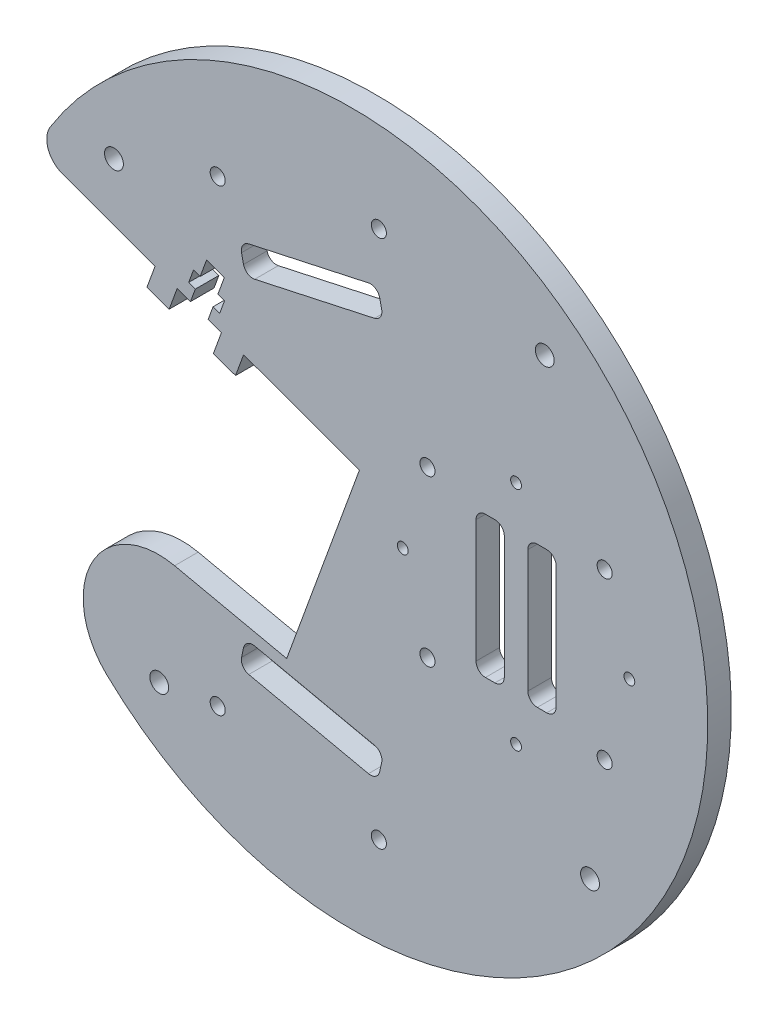
SolidWorks part; units mm, degrees
ref_plane "Plan de face" through (0, 0, 0) normal (0, 0, 1) x (1, 0, 0)
ref_plane "Plan de dessus" through (0, 0, 0) normal (0, 1, 0) x (1, 0, 0)
ref_plane "Plan de droite" through (0, 0, 0) normal (1, 0, 0) x (0, 0, -1)
sketch "Esquisse1" plane through (0, 0, 0) normal (0, 0, 1) x (1, 0, 0)
  line L0 (-41.7896, 25.5149) -> (-67.0437, 34.7187)
  line L3 (-22.9986, 18.6666) -> (1.5696, 9.7128)
  line L4 (1.5696, 9.7128) -> (-13.858, -32.6189)
  line L5 (-13.858, -32.6189) -> (-72.862, -19.7834)
  line L6 (-40.9058, -50.5145) -> (40.9058, 50.5145) construction
  line L7 (0, 0) -> (50.5145, -40.9058) construction
  line L8 (0, 0) -> (-50.5145, 40.9058) construction
  circle A0 centre (0, 0) radius 75.5 construction
  arc A1 (-67.0437, 34.7187) -> (-72.862, -19.7834) centre (0, 0) cw
  circle A2 centre (0, 0) radius 65 construction
  circle A3 centre (40.9058, 50.5145) radius 2
  circle A4 centre (-50.5145, 40.9058) radius 2
  circle A5 centre (50.5145, -40.9058) radius 2
  circle A6 centre (-40.9058, -50.5145) radius 2
  point P4 (-36.0291, 0)
  point P13 (-11.3975, 52.3938)
  point P22 (34.8192, 0)
  line B0 (-28.4976, 48.6739) -> (5.7025, 56.1137) construction
  line B1 (-14.416, 66.2693) -> (-7.4013, 34.0235) construction
  line B2 (-45.6847, 59.4672) -> (16.8527, 73.0714) construction
  line B3 (-49.5076, 53.5187) -> (-43.5558, 26.1586) construction
  line B4 (-43.5558, 26.1586) -> (28.7531, 41.8884) construction
  line B5 (22.8013, 69.2485) -> (28.7531, 41.8884) construction
  circle B6 centre (-28.4976, 48.6739) radius 1.6
  circle B7 centre (5.7025, 56.1137) radius 1.6
  circle B8 centre (5.7025, 56.1137) radius 16.6 construction
  circle B9 centre (-28.4976, 48.6739) radius 16.6 construction
  arc B10 (-45.6847, 59.4672) -> (-49.5076, 53.5187) centre (-44.6218, 54.5815) ccw construction
  arc B11 (16.8527, 73.0714) -> (22.8013, 69.2485) centre (17.9156, 68.1856) cw construction
  line B12 (-23.0151, 35.2322) -> (-23.4402, 37.1864)
  line B13 (-20.6357, 33.703) -> (4.7702, 39.2297)
  line B14 (6.2993, 41.6091) -> (5.8742, 43.5634)
  line B15 (-21.911, 39.5659) -> (3.4948, 45.0926)
  line B16 (-23.2276, 36.2093) -> (6.0868, 42.5862) construction
  arc B17 (3.4948, 45.0926) -> (5.8742, 43.5634) centre (3.9199, 43.1383) cw
  arc B18 (4.7702, 39.2297) -> (6.2993, 41.6091) centre (4.345, 41.184) ccw
  arc B19 (-20.6357, 33.703) -> (-23.0151, 35.2322) centre (-21.0608, 35.6573) cw
  arc B20 (-23.4402, 37.1864) -> (-21.911, 39.5659) centre (-21.4859, 37.6116) cw
  line B21 (5.7025, -56.1137) -> (-28.4976, -48.6739) construction
  line B22 (-14.416, -66.2693) -> (-7.4013, -34.0235) construction
  line B23 (16.8527, -73.0714) -> (-45.6847, -59.4672) construction
  line B24 (22.8013, -69.2485) -> (28.7531, -41.8884) construction
  line B25 (28.7531, -41.8884) -> (-43.5558, -26.1586) construction
  line B26 (-49.5076, -53.5187) -> (-43.5558, -26.1586) construction
  circle B27 centre (5.7025, -56.1137) radius 1.6
  circle B28 centre (-28.4976, -48.6739) radius 1.6
  circle B29 centre (-28.4976, -48.6739) radius 16.6 construction
  circle B30 centre (5.7025, -56.1137) radius 16.6 construction
  arc B31 (16.8527, -73.0714) -> (22.8013, -69.2485) centre (17.9156, -68.1856) ccw construction
  arc B32 (-45.6847, -59.4672) -> (-49.5076, -53.5187) centre (-44.6218, -54.5815) cw construction
  line B33 (6.2993, -41.6091) -> (5.8742, -43.5634)
  line B34 (4.7702, -39.2297) -> (-20.6357, -33.703)
  line B35 (-23.0151, -35.2322) -> (-23.4402, -37.1864)
  line B36 (3.4948, -45.0926) -> (-21.911, -39.5659)
  line B37 (6.0868, -42.5862) -> (-23.2276, -36.2093) construction
  arc B38 (-21.911, -39.5659) -> (-23.4402, -37.1864) centre (-21.4859, -37.6116) cw
  arc B39 (-20.6357, -33.703) -> (-23.0151, -35.2322) centre (-21.0608, -35.6573) ccw
  arc B40 (4.7702, -39.2297) -> (6.2993, -41.6091) centre (4.345, -41.184) cw
  arc B41 (5.8742, -43.5634) -> (3.4948, -45.0926) centre (3.9199, -43.1383) cw
  line B42 (53.6192, 17.5) -> (53.6192, -17.5) construction
  line B43 (67.8192, 0) -> (34.8192, 0) construction
  line B44 (67.8192, 32) -> (67.8192, -32) construction
  line B45 (62.8192, 37) -> (34.8192, 37) construction
  line B46 (34.8192, 37) -> (34.8192, -37) construction
  line B47 (62.8192, -37) -> (34.8192, -37) construction
  circle B48 centre (53.6192, 17.5) radius 1.6
  circle B49 centre (53.6192, -17.5) radius 1.6
  circle B50 centre (53.6192, -17.5) radius 16.6 construction
  circle B51 centre (53.6192, 17.5) radius 16.6 construction
  arc B52 (67.8192, 32) -> (62.8192, 37) centre (62.8192, 32) ccw construction
  arc B53 (67.8192, -32) -> (62.8192, -37) centre (62.8192, -32) cw construction
  line B54 (39.3192, 15) -> (41.3192, 15)
  line B55 (37.3192, 13) -> (37.3192, -13)
  line B56 (39.3192, -15) -> (41.3192, -15)
  line B57 (43.3192, 13) -> (43.3192, -13)
  line B58 (40.3192, 15) -> (40.3192, -15) construction
  arc B59 (43.3192, -13) -> (41.3192, -15) centre (41.3192, -13) cw
  arc B60 (37.3192, -13) -> (39.3192, -15) centre (39.3192, -13) ccw
  arc B61 (37.3192, 13) -> (39.3192, 15) centre (39.3192, 13) cw
  arc B62 (41.3192, 15) -> (43.3192, 13) centre (41.3192, 13) cw
  line B63 (16.0192, -17.5) -> (16.0192, 17.5) construction
  line B64 (1.8192, 0) -> (34.8192, 0) construction
  line B65 (1.8192, -32) -> (1.8192, 32) construction
  line B66 (6.8192, -37) -> (34.8192, -37) construction
  line B67 (34.8192, -37) -> (34.8192, 37) construction
  line B68 (6.8192, 37) -> (34.8192, 37) construction
  circle B69 centre (16.0192, -17.5) radius 1.6
  circle B70 centre (16.0192, 17.5) radius 1.6
  circle B71 centre (16.0192, 17.5) radius 16.6 construction
  circle B72 centre (16.0192, -17.5) radius 16.6 construction
  arc B73 (1.8192, -32) -> (6.8192, -37) centre (6.8192, -32) ccw construction
  arc B74 (1.8192, 32) -> (6.8192, 37) centre (6.8192, 32) cw construction
  line B75 (30.3192, -15) -> (28.3192, -15)
  line B76 (32.3192, -13) -> (32.3192, 13)
  line B77 (30.3192, 15) -> (28.3192, 15)
  line B78 (26.3192, -13) -> (26.3192, 13)
  line B79 (29.3192, -15) -> (29.3192, 15) construction
  arc B80 (26.3192, 13) -> (28.3192, 15) centre (28.3192, 13) cw
  arc B81 (32.3192, 13) -> (30.3192, 15) centre (30.3192, 13) ccw
  arc B82 (32.3192, -13) -> (30.3192, -15) centre (30.3192, -13) cw
  arc B83 (28.3192, -15) -> (26.3192, -13) centre (28.3192, -13) cw
  line B84 (-11.7846, -26.9296) -> (-71.9157, -5.015) construction
  line B85 (-71.9157, -5.015) -> (-60.2736, 26.9296) construction
  line B86 (-60.2736, 26.9296) -> (-0.1425, 5.015) construction
  line B87 (-0.1425, 5.015) -> (-11.7846, -26.9296) construction
  line B88 (-11.7846, -26.9296) -> (-60.2736, 26.9296) construction
  line B89 (-71.9157, -5.015) -> (-0.1425, 5.015) construction
  line B90 (-34.6552, 26.1078) -> (-33.628, 28.9265)
  line B91 (-28.4605, 27.0432) -> (-27.0908, 30.8014)
  line B92 (-30.849, 32.171) -> (-32.2187, 28.4128)
  line B93 (-33.628, 28.9265) -> (-32.2187, 28.4128)
  line B94 (-32.3941, 22.0907) -> (-28.5519, 32.6332) construction
  line B95 (-34.2732, 22.7756) -> (-37.0918, 23.8028)
  line B96 (-38.8039, 19.1051) -> (-43.5016, 20.8171)
  line B97 (-43.5016, 20.8171) -> (-41.7896, 25.5149)
  line B98 (-38.8039, 19.1051) -> (-37.0918, 23.8028)
  line B99 (-30.515, 21.4059) -> (-27.6963, 20.3786)
  line B100 (-27.6963, 20.3786) -> (-29.4084, 15.6809)
  line B101 (-29.4084, 15.6809) -> (-24.7107, 13.9688)
  line B102 (-24.7107, 13.9688) -> (-22.9986, 18.6666)
  line B103 (-34.2732, 22.7756) -> (-30.515, 21.4059) construction
  line B104 (-30.515, 21.4059) -> (-29.4877, 24.2245)
  line B105 (-28.4605, 27.0432) -> (-27.0512, 26.5296)
  line B106 (-28.0784, 23.7109) -> (-29.4877, 24.2245)
  line B107 (-27.0908, 30.8014) -> (-30.849, 32.171)
  line B108 (-33.2459, 25.5942) -> (-34.6552, 26.1078)
  line B109 (-27.0512, 26.5296) -> (-28.0784, 23.7109)
  line B110 (-33.2459, 25.5942) -> (-34.2732, 22.7756)
  line B111 (-28.9699, 31.4862) -> (-32.3941, 22.0907) construction
  line B112 (10.7776, 0) -> (34.8192, 24.0416) construction
  line B113 (34.8192, 24.0416) -> (58.8608, 0) construction
  line B114 (58.8608, 0) -> (34.8192, -24.0416) construction
  line B115 (34.8192, -24.0416) -> (10.7776, 0) construction
  line B116 (6.5349, 0) -> (34.8192, -28.2843) construction
  line B117 (34.8192, -28.2843) -> (63.1035, 0) construction
  line B118 (63.1035, 0) -> (34.8192, 28.2843) construction
  line B119 (34.8192, 28.2843) -> (6.5349, 0) construction
  line B120 (6.5349, 0) -> (63.1035, 0) construction
  line B121 (20.677, 14.1421) -> (48.9613, -14.1421) construction
  circle B122 centre (10.7776, 0) radius 1.15
  circle B123 centre (34.8192, 24.0416) radius 1.15
  circle B124 centre (58.8608, 0) radius 1.15
  circle B125 centre (34.8192, -24.0416) radius 1.15
  dimension "D1" = 151
  dimension "D3" = 38
  dimension "D4" = 130
  dimension "D5" = 4
  dimension "D2" = 6
  dimension "D6" = 39
sketch_block_instance "Bloc1-1"
sketch_block "Bloc1" parameters "D2"=3.2, "D6"=33.2, "D7"=5, "D11"=2, "D1"=35, "D3"=74, "D4"=33, "D5"=18.8, "D8"=25.4437, "D9"=7.7224, "D10"=25.4437
sketch_block_instance "Bloc1-3"
sketch_block_instance "Bloc1-4"
sketch_block_instance "Bloc1-5"
sketch_block_instance "Bloc2-1"
sketch_block "Bloc2" parameters "D1"=34, "D2"=64
sketch_block_instance "Insert M4 plots ep 5mm-1"
sketch_block "Insert M4 plots ep 5mm" parameters "D1"=10, "D2"=5, "D3"=5, "D4"=7, "D5"=4, "D6"=3, "D7"=3, "D8"=10
sketch_block_instance "Bloc3-1"
sketch_block "Bloc3" parameters "D4"=2.3, "D1"=34, "D2"=40, "D3"=3
extrude "Boss.-Extru.1" add sketch "Esquisse1" along normal blind 5 contours B110 B108 B90 B93 B92 B107 B91 B105 B109 B106 B104 B99 B100 B101 B102 L3 L4 L5 A1 L0 B97 B96 B98 B95 B70 B69 B49 B48 B28 B27 B7 B6 B12 B20 B15 B17 B14 B18 B13 B19 B33 region at (9.6176, 0.1061, 0)
fillet "Congé1" radius 16 1 edges at (-72.862, -19.7834, 2.5)
fillet "Congé2" radius 5 1 edges at (-67.0437, 34.7187, 2.5)
